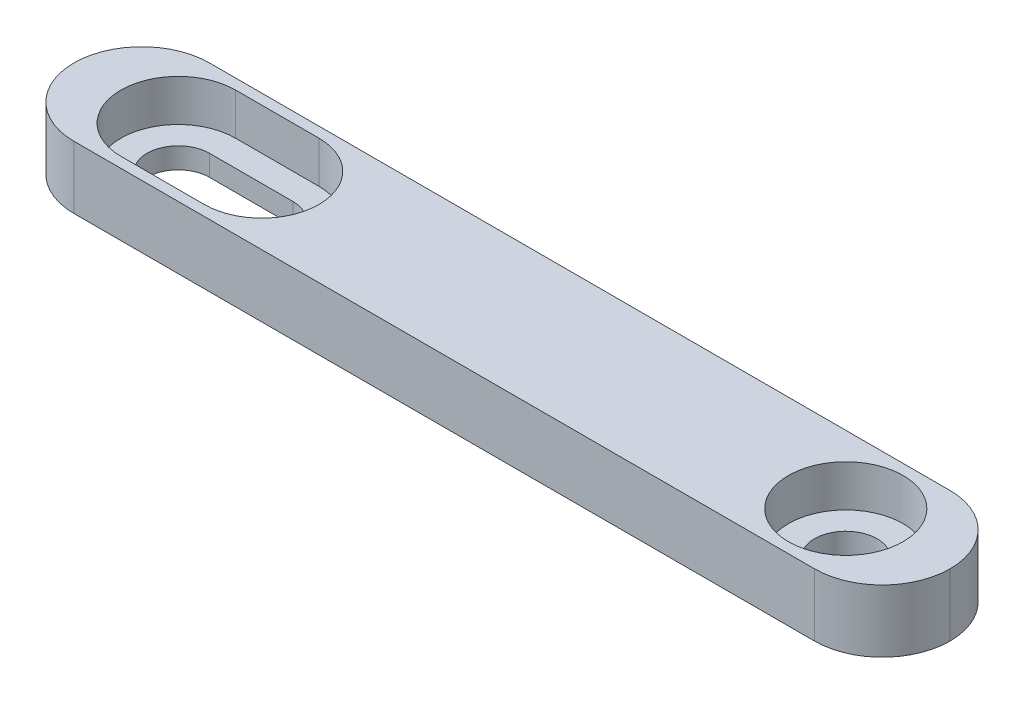
SolidWorks part; units mm, degrees
ref_plane "Plano frontal" through (0, 0, 0) normal (0, 0, 1) x (1, 0, 0)
ref_plane "Plano superior" through (0, 0, 0) normal (0, 1, 0) x (1, 0, 0)
ref_plane "Plano direito" through (0, 0, 0) normal (1, 0, 0) x (0, 0, -1)
sketch "Esboço1" plane through (0, 0, 0) normal (0, 1, 0) x (1, 0, 0)
  line L1 (21, -3.25) -> (-21, -3.25)
  line L2 (21, -3.25) -> (21, 3.25)
  line L3 (21, 3.25) -> (-21, 3.25)
  line L4 (-21, -3.25) -> (-21, 3.25)
  line L5 (21, -3.25) -> (-21, 3.25) construction
  line L6 (21, 3.25) -> (-21, -3.25) construction
  point P0 (0, 0)
  dimension "D1" = 6.5
  dimension "D2" = 42
extrude "Ressalto-extrusão1" add sketch "Esboço1" along normal blind 3
sketch "Esboço2" plane through (0, 3, 0) normal (0, 1, 0) x (1, 0, 0)
  line L0 (-20.4106, 0) -> (22.516, 0) construction
  line L1 (0, 7.0837) -> (0, -9.8179) construction
  line L2 (-16, 0) -> (-12, 0) construction
  line L3 (21, -3.25) -> (21, 3.25) construction
  line L4 (-16, 1.5) -> (-12, 1.5)
  line L5 (-16, -1.5) -> (-12, -1.5)
  line L6 (-21, 3.25) -> (-21, -3.25) construction
  circle A2 centre (16, 0) radius 1.5
  arc A6 (-16, 1.5) -> (-16, -1.5) centre (-16, 0) ccw
  arc A7 (-12, -1.5) -> (-12, 1.5) centre (-12, 0) ccw
  point P7 (-14, 0)
  dimension "D1" = 5
  dimension "D3" = 5
  dimension "D4" = 3
  dimension "D2" = 1.5
  dimension "D5" = 4
extrude "Corte-extrusão1" cut sketch "Esboço2" against normal through all
sketch "Esboço3" plane through (0, 3, 0) normal (0, 1, 0) x (1, 0, 0)
  line L0 (-25.4986, 0) -> (27.7795, 0) construction
  line L1 (0, 5.5531) -> (0, -5.7341) construction
  line L2 (-16, 0) -> (-12, 0) construction
  line L3 (-16, 2.75) -> (-12, 2.75)
  line L4 (-16, -2.75) -> (-12, -2.75)
  line L5 (-21, 3.25) -> (-21, -3.25) construction
  circle A3 centre (16, 0) radius 2.75
  arc A6 (-16, 2.75) -> (-16, -2.75) centre (-16, 0) ccw
  arc A7 (-12, -2.75) -> (-12, 2.75) centre (-12, 0) ccw
  point P9 (-14, 0)
  dimension "D1" = 5.5
  dimension "D2" = 2.75
  dimension "D3" = 5
  dimension "D4" = 4
extrude "Corte-extrusão2" cut sketch "Esboço3" against normal blind 2
fillet "Filete1" radius 3.25 4 edges at (21, 1.5, 3.25) (21, 1.5, -3.25) (-21, 1.5, 3.25) (-21, 1.5, -3.25)
